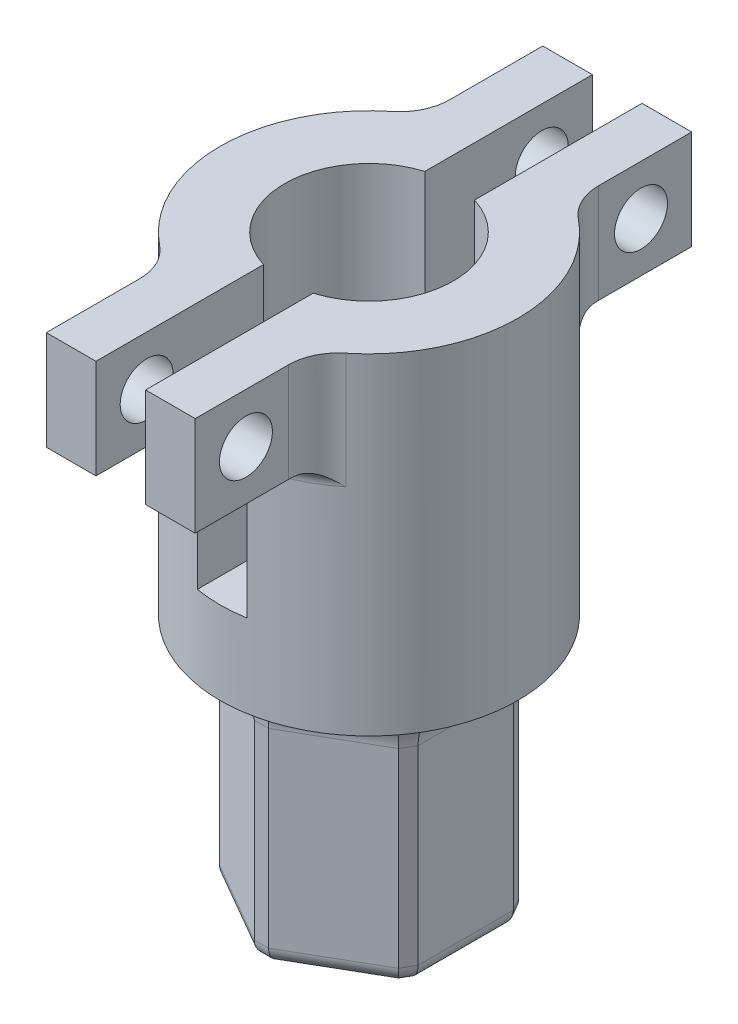
SolidWorks part; units mm, degrees
ref_plane "Front Plane" through (0, 0, 0) normal (0, 0, 1) x (1, 0, 0)
ref_plane "Top Plane" through (0, 0, 0) normal (0, 1, 0) x (1, 0, 0)
ref_plane "Right Plane" through (0, 0, 0) normal (1, 0, 0) x (0, 0, -1)
sketch "Sketch1" plane through (0, 0, 0) normal (0, 1, 0) x (1, 0, 0)
  line L0 (0, 6.75) -> (5.8457, 3.375)
  line L1 (5.8457, 3.375) -> (5.8457, -3.375)
  line L2 (5.8457, -3.375) -> (0, -6.75)
  line L3 (0, -6.75) -> (-5.8457, -3.375)
  line L4 (-5.8457, -3.375) -> (-5.8457, 3.375)
  line L5 (-5.8457, 3.375) -> (0, 6.75)
  circle A0 centre (0, 0) radius 6.75 construction
  circle A2 centre (0, 0) radius 1.5
  dimension "D1" = 13.5
  dimension "D2" = 3
extrude "Boss-Extrude1" add sketch "Sketch1" along normal blind 15
sketch "Sketch2" plane through (0, 15, 0) normal (0, 1, 0) x (1, 0, 0)
  circle A0 centre (0, 0) radius 9
  dimension "D1" = 18
extrude "Boss-Extrude2" add sketch "Sketch2" along normal blind 5
sketch "Sketch3" plane through (0, 20, 0) normal (0, 1, 0) x (1, 0, 0)
  circle A0 centre (0, 0) radius 9
  circle A1 centre (0, 0) radius 5.1
  circle A2 centre (0, 0) radius 9 construction
  dimension "D1" = 10.2
extrude "Boss-Extrude3" add sketch "Sketch3" along normal blind 15
sketch "Sketch4" plane through (0, 35, 0) normal (0, 1, 0) x (1, 0, 0)
  line L1 (-1.5, 9) -> (1.5, 9)
  line L2 (-1.5, 9) -> (-1.5, -9)
  line L3 (-1.5, -9) -> (1.5, -9)
  line L4 (1.5, 9) -> (1.5, -9)
  circle A0 centre (0, 0) radius 9 construction
  point P4 (0, 9)
  dimension "D1" = 3
extrude "Cut-Extrude1" cut sketch "Sketch4" against normal blind 15
sketch "Sketch5" plane through (1.5, 0, 0) normal (-1, 0, 0) x (0, 0, 1)
  line L0 (8.8741, 35) -> (4.8744, 35) construction
  line L1 (-15, 35) -> (15, 35)
  line L2 (-15, 35) -> (-15, 29)
  line L3 (-15, 29) -> (15, 29)
  line L4 (15, 35) -> (15, 29)
  line L6 (-4.8744, 35) -> (4.8744, 35)
  line L7 (-4.8744, 35) -> (-4.8744, 29)
  line L8 (-4.8744, 29) -> (4.8744, 29)
  line L9 (4.8744, 35) -> (4.8744, 29)
  line L10 (-4.8744, 20) -> (-4.8744, 35) construction
  line L11 (-8.8741, 35) -> (-8.8741, 29) construction
  line L12 (-8.8741, 35) -> (-8.8741, 20) construction
  line L13 (-15, 35) -> (-8.8741, 29) construction
  line L14 (-8.8741, 35) -> (-15, 29) construction
  line L15 (0, 35) -> (0, 29) construction
  circle A0 centre (-11.9371, 32) radius 1.6
  circle A1 centre (11.9371, 32) radius 1.6
  point P10 (0, 35)
  point P11 (0, 35)
  point P14 (0, 29)
  point P23 (-11.9371, 32)
  line M14 (8.8741, 35) -> (4.8744, 35)
  line M15 (4.8744, 35) -> (4.8744, 20)
  line M17 (8.8741, 20) -> (8.8741, 35)
  dimension "D3" = 3.2
  dimension "D1" = 30
  dimension "D2" = 6
extrude "Boss-Extrude4" add sketch "Sketch5" against normal blind 3 and the other way blind 6 contours L7 L1 L2 L3 A0 | L4 L1 L3 A1 M17 | L3 M15 M17 M14 region at (1.5, 32, -9.6321) region at (1.5, 32, 6.8743) region at (1.5, 34.9143, 11.9371)
sketch "Sketch6" plane through (0, 35, 0) normal (0, 1, 0) x (1, 0, 0)
  line L0 (-4.5, 15) -> (4.5, 15) construction
  line L1 (-1.5, 15) -> (1.5, 15)
  line L2 (-1.5, 15) -> (-1.5, -15)
  line L3 (-1.5, -15) -> (1.5, -15)
  line L4 (1.5, 15) -> (1.5, -15)
  line L5 (4.5, -15) -> (-4.5, -15) construction
  point P8 (0, -15)
  dimension "D1" = 3
extrude "Cut-Extrude2" cut sketch "Sketch6" against normal up to surface (15 mm away) up to face at (0, 20, 0)
fillet "Fillet4" radius 3 4 edges at (-4.5, 32, -7.7942) (-4.5, 32, 7.7942) (4.5, 32, -7.7942) (4.5, 32, 7.7942)
fillet "Fillet5" radius 1 4 edges at (3.6804, 29, -8.2131) (-3.6804, 29, -8.2131) (3.6804, 29, 8.2131) (-3.6804, 29, 8.2131)
chamfer "Chamfer2" distance 0.5 angle 30 6 edges at (-5.8457, 7.5, -3.375) (0, 7.5, -6.75) (5.8457, 7.5, -3.375) (-5.8457, 7.5, 3.375) (0, 7.5, 6.75) (5.8457, 7.5, 3.375) first distance on face at (-5.8457, 7.5, 0) first distance on face at (2.9228, 7.5, -5.0625) first distance on face at (2.9228, 7.5, 5.0625)
fillet "Fillet6" radius 1 12 edges at (5.6292, 0, 3.25) (-5.6292, 0, -3.25) (-5.8457, 0, 0) (0, 0, 6.5) (-5.6292, 0, 3.25) (-2.9228, 0, 5.0625) (2.9228, 0, 5.0625) (5.8457, 0, 0) (5.6292, 0, -3.25) (0, 0, -6.5) (-2.9228, 0, -5.0625) (2.9228, 0, -5.0625)
fillet "Fillet7" radius 2.5 12 edges at (5.6292, 15, 3.25) (2.9228, 15, 5.0625) (0, 15, 6.5) (-2.9228, 15, 5.0625) (-5.6292, 15, 3.25) (-5.8457, 15, 0) (-5.6292, 15, -3.25) (-2.9228, 15, -5.0625) (0, 15, -6.5) (2.9228, 15, -5.0625) (5.6292, 15, -3.25) (5.8457, 15, 0)
